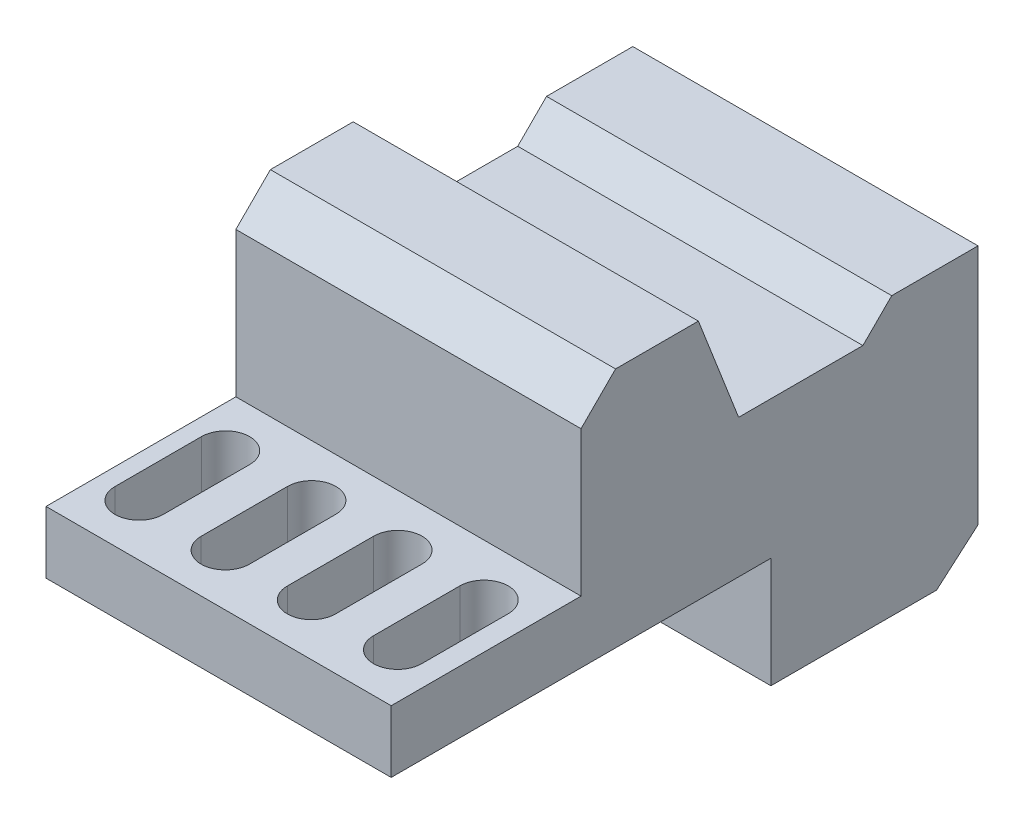
SolidWorks part; units mm, degrees
ref_plane "Plano frontal" through (0, 0, 0) normal (0, 0, 1) x (1, 0, 0)
ref_plane "Plano superior" through (0, 0, 0) normal (0, 1, 0) x (1, 0, 0)
ref_plane "Plano direito" through (0, 0, 0) normal (1, 0, 0) x (0, 0, -1)
sketch "Esboço3" plane through (0, 0, 0) normal (1, 0, 0) x (0, 0, -1)
  line L0 (0, 0) -> (0, -70)
  line L1 (0, 0) -> (-25, 0)
  line L2 (-12, -80.38) -> (-60, -80.38)
  line L3 (-25, 0) -> (-33.3439, -8.3439)
  line L4 (-33.3439, -8.3439) -> (-69.3439, -8.3439)
  line L5 (-60, -80.38) -> (-60, -48.3785)
  line L6 (-69.3439, -8.3439) -> (-81.0015, 21.62)
  line L7 (-81.0015, 21.62) -> (-105.0015, 21.62)
  line L8 (-105.0015, 21.62) -> (-115, 11.6215)
  line L9 (-115, 11.6215) -> (-115, -30.3785)
  line L10 (-115, -30.3785) -> (-170, -30.3785)
  line L11 (-170, -30.3785) -> (-170, -48.3785)
  line L12 (-170, -48.3785) -> (-60, -48.3785)
  line L13 (0, -70) -> (-12, -80.38)
  point P5 (0, -70)
  point P8 (-12, -80.38)
  dimension "D1" = 18
  dimension "D2" = 25
  dimension "D3" = 55
  dimension "D4" = 11.8
  dimension "D5" = 36
  dimension "D6" = 110
  dimension "D7" = 102
  dimension "D8" = 42
  dimension "D9" = 14.14
  dimension "D10" = 24
  dimension "D11" = 80.38
  dimension "D12" = 70
  dimension "D13" = 158
extrude "Ressalto-extrusão1" add sketch "Esboço3" along normal blind 100
sketch "Esboço5" plane through (0, -30.3785, 0) normal (0, 1, 0) x (1, 0, 0)
  line L0 (0, -142.5) -> (100, -142.5) construction
  line L1 (0, -115) -> (0, -170) construction
  line L2 (100, -115) -> (100, -170) construction
  line L3 (12, -155.02) -> (12, -129.98) construction
  line L4 (5, -155.02) -> (5, -129.98)
  line L5 (19, -155.02) -> (19, -129.98)
  line L6 (36.96, -155.02) -> (36.96, -129.98) construction
  line L7 (29.96, -155.02) -> (29.96, -129.98)
  line L8 (43.96, -155.02) -> (43.96, -129.98)
  line L9 (61.92, -155.02) -> (61.92, -129.98) construction
  line L10 (54.92, -155.02) -> (54.92, -129.98)
  line L11 (68.92, -155.02) -> (68.92, -129.98)
  line L12 (86.88, -155.02) -> (86.88, -129.98) construction
  line L13 (79.88, -155.02) -> (79.88, -129.98)
  line L14 (93.88, -155.02) -> (93.88, -129.98)
  line L15 (12, -155.02) -> (36.96, -155.02) construction
  arc A0 (5, -155.02) -> (19, -155.02) centre (12, -155.02) ccw
  arc A1 (19, -129.98) -> (5, -129.98) centre (12, -129.98) ccw
  arc A2 (29.96, -155.02) -> (43.96, -155.02) centre (36.96, -155.02) ccw
  arc A3 (43.96, -129.98) -> (29.96, -129.98) centre (36.96, -129.98) ccw
  arc A4 (54.92, -155.02) -> (68.92, -155.02) centre (61.92, -155.02) ccw
  arc A5 (68.92, -129.98) -> (54.92, -129.98) centre (61.92, -129.98) ccw
  arc A6 (79.88, -155.02) -> (93.88, -155.02) centre (86.88, -155.02) ccw
  arc A7 (93.88, -129.98) -> (79.88, -129.98) centre (86.88, -129.98) ccw
  point P8 (12, -142.5)
  point P16 (36.96, -142.5)
  point P23 (61.92, -142.5)
  point P30 (86.88, -142.5)
  dimension "D1" = 12.52
  dimension "D2" = 7
  dimension "D3" = 5
  dimension "D5" = 24.96
  dimension "D4" = 4
extrude "Corte-extrusão1" cut sketch "Esboço5" against normal through all
